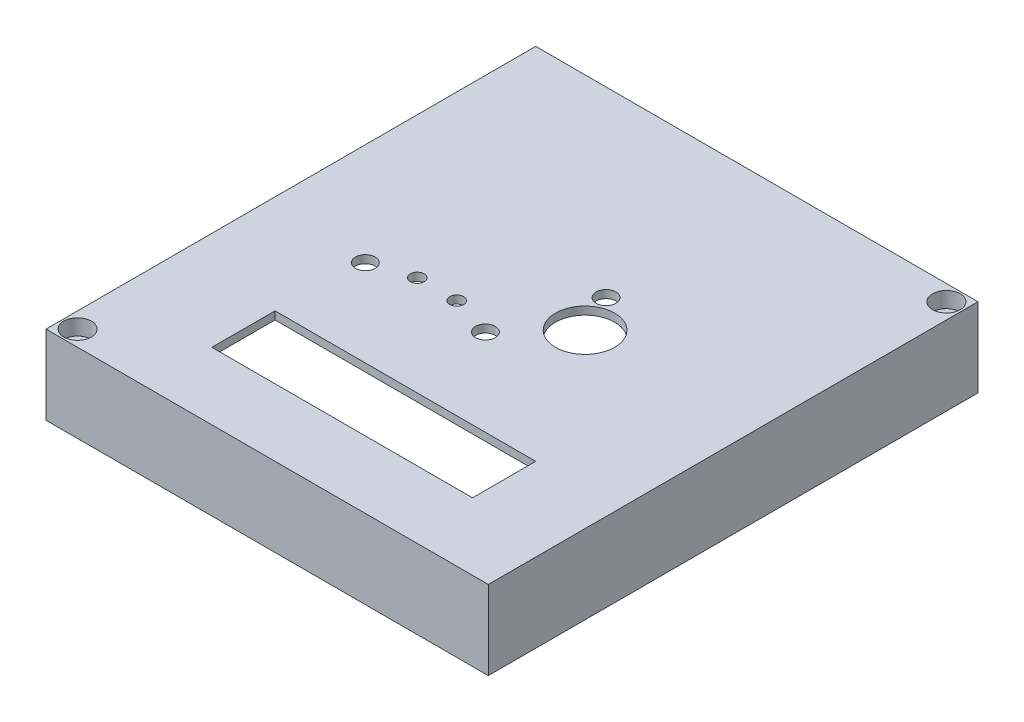
SolidWorks part; units mm, degrees
ref_plane "Front Plane" through (0, 0, 0) normal (0, 0, 1) x (1, 0, 0)
ref_plane "Top Plane" through (0, 0, 0) normal (0, 1, 0) x (1, 0, 0)
ref_plane "Right Plane" through (0, 0, 0) normal (1, 0, 0) x (0, 0, -1)
sketch "Sketch1" plane through (0, 0, 0) normal (0, 1, 0) x (1, 0, 0)
  line L1 (-56, -62) -> (56, -62)
  line L2 (-56, -62) -> (-56, 62)
  line L3 (-56, 62) -> (56, 62)
  line L4 (56, -62) -> (56, 62)
  line L5 (-56, -62) -> (56, 62) construction
  line L6 (-56, 62) -> (56, -62) construction
  point P0 (0, 0)
  dimension "D1" = 112
  dimension "D2" = 124
extrude "Boss-Extrude1" add sketch "Sketch1" along normal blind 2
sketch "Sketch4" plane through (0, 0, 0) normal (0, -1, 0) x (1, 0, 0)
  line L0 (-48, 58) -> (-48, 54)
  line L1 (-48, 54) -> (-52, 54)
  line L2 (48, -58) -> (48, -54)
  line L3 (48, -54) -> (52, -54)
  line L4 (56, -62) -> (56, 62)
  line L5 (56, 62) -> (-56, 62)
  line L6 (-56, 62) -> (-56, -62)
  line L7 (-56, -62) -> (56, -62)
  line L8 (56, -62) -> (56, 62)
  line L9 (56, 62) -> (-56, 62)
  line L10 (-56, 62) -> (-56, -62)
  line L11 (-56, -62) -> (56, -62)
  line L24 (52, -58) -> (52, 58)
  line L25 (52, 58) -> (-52, 58)
  line L26 (-52, 58) -> (-52, -58)
  line L27 (-52, -58) -> (52, -58)
  line L28 (52, -54) -> (52, 58)
  line L29 (52, 58) -> (-48, 58)
  line L30 (-52, 54) -> (-52, -58)
  line L31 (-52, -58) -> (48, -58)
  dimension "D4" = 4
  dimension "D6" = 4
  dimension "D1" = 0
  dimension "D2" = 4
extrude "Boss-Extrude2" add sketch "Sketch4" along normal blind 18
sketch "Sketch5" plane through (0, 2, 0) normal (0, 1, 0) x (1, 0, 0)
  line L0 (-56, -62) -> (56, -62) construction
  line L1 (-31, -45) -> (35, -45)
  line L2 (-31, -45) -> (-31, -29)
  line L3 (-31, -29) -> (35, -29)
  line L4 (35, -45) -> (35, -29)
  line L5 (-31, -45) -> (35, -29) construction
  line L6 (-31, -29) -> (35, -45) construction
  line L10 (-56, 62) -> (-56, -62) construction
  circle A0 centre (12.5, 6) radius 7.5
  circle A1 centre (-30.13, -7.01) radius 2.5
  circle A2 centre (-20.25, -3.7495) radius 1.75
  circle A3 centre (-10.25, -3.7495) radius 1.75
  circle A4 centre (0.2695, -7.01) radius 2.5
  circle A5 centre (8.001, 15.811) radius 2.5
  point P0 (2, -37)
  point P8 (0, 0)
  dimension "D4" = 15
  dimension "D8" = 5
  dimension "D9" = 3.5
  dimension "D5" = 47.999
  dimension "D6" = 46.189
  dimension "D10" = 43.5
  dimension "D12" = 55.7305
  dimension "D13" = 69.01
  dimension "D14" = 66.25
  dimension "D15" = 65.7495
  dimension "D16" = 65.7495
  dimension "D17" = 76.25
  dimension "D18" = 86.13
  dimension "D19" = 69.01
  dimension "D1" = 66
  dimension "D2" = 16
  dimension "D3" = 17
  dimension "D7" = 25
  dimension "D11" = 56
extrude "Cut-Extrude1" cut sketch "Sketch5" against normal up to next contours A0 | A4 | A3 | A2 | A1 | L1 L4 L3 L2 | A5 region at (2, 2, 37) region at (12.5, 2, -6) region at (-30.13, 2, 7.01) region at (-20.25, 2, 3.7495) region at (-10.25, 2, 3.7495) region at (0.2695, 2, 7.01) region at (8.001, 2, -15.811)
sketch "Sketch6" plane through (0, 2, 0) normal (0, 1, 0) x (1, 0, 0)
  line L0 (56, 62) -> (-56, 62) construction
  line L1 (56, -62) -> (56, 62) construction
  line L2 (-56, -62) -> (56, -62) construction
  line L3 (-56, 62) -> (-56, -62) construction
  circle A0 centre (52, 58) radius 2
  circle A1 centre (-52, -58) radius 2
  dimension "D1" = 4
  dimension "D4" = 4
  dimension "D2" = 4
  dimension "D3" = 4
  dimension "D5" = 4
  dimension "D6" = 4
extrude "Cut-Extrude2" cut sketch "Sketch6" against normal through all
sketch "Sketch7" plane through (0, 2, 0) normal (0, 1, 0) x (1, 0, 0)
  circle A0 centre (-52, -58) radius 3.5
  circle A1 centre (52, 58) radius 3.5
  dimension "D1" = 7
  dimension "D2" = 7
extrude "Cut-Extrude3" cut sketch "Sketch7" against normal blind 4
sketch "Sketch8" plane through (-56, 0, 0) normal (-1, 0, 0) x (0, 0, 1)
  line L7 (-48.75, -7.6872) -> (-40.75, -7.6872) construction
  line L8 (-48.75, -2.6872) -> (-40.75, -2.6872)
  line L9 (-48.75, -12.6872) -> (-40.75, -12.6872)
  line L10 (-27.75, -7.6872) -> (-19.75, -7.6872) construction
  line L11 (-27.75, -2.6872) -> (-19.75, -2.6872)
  line L12 (-27.75, -12.6872) -> (-19.75, -12.6872)
  line L13 (-4.5, -7.6872) -> (0.5, -7.6872) construction
  line L14 (-4.5, -4.6872) -> (0.5, -4.6872)
  line L15 (-4.5, -10.6872) -> (0.5, -10.6872)
  line L16 (-62, 2) -> (-62, -18) construction
  arc A0 (-48.75, -2.6872) -> (-48.75, -12.6872) centre (-48.75, -7.6872) ccw
  arc A1 (-40.75, -12.6872) -> (-40.75, -2.6872) centre (-40.75, -7.6872) ccw
  arc A2 (-27.75, -2.6872) -> (-27.75, -12.6872) centre (-27.75, -7.6872) ccw
  arc A3 (-19.75, -12.6872) -> (-19.75, -2.6872) centre (-19.75, -7.6872) ccw
  arc A4 (-4.5, -4.6872) -> (-4.5, -10.6872) centre (-4.5, -7.6872) ccw
  arc A5 (0.5, -10.6872) -> (0.5, -4.6872) centre (0.5, -7.6872) ccw
  point P2 (-44.75, -7.6872)
  point P8 (-23.75, -7.6872)
  point P15 (-2, -7.6872)
  point P23 (-53.75, -7.6872)
  point P24 (-35.75, -7.6872)
  dimension "D2" = 5
  dimension "D3" = 3
  dimension "D1" = 18
  dimension "D4" = 5
  dimension "D5" = 13.25
  dimension "D6" = 34.25
  dimension "D7" = 60
extrude "Cut-Extrude4" cut sketch "Sketch8" against normal blind 20
